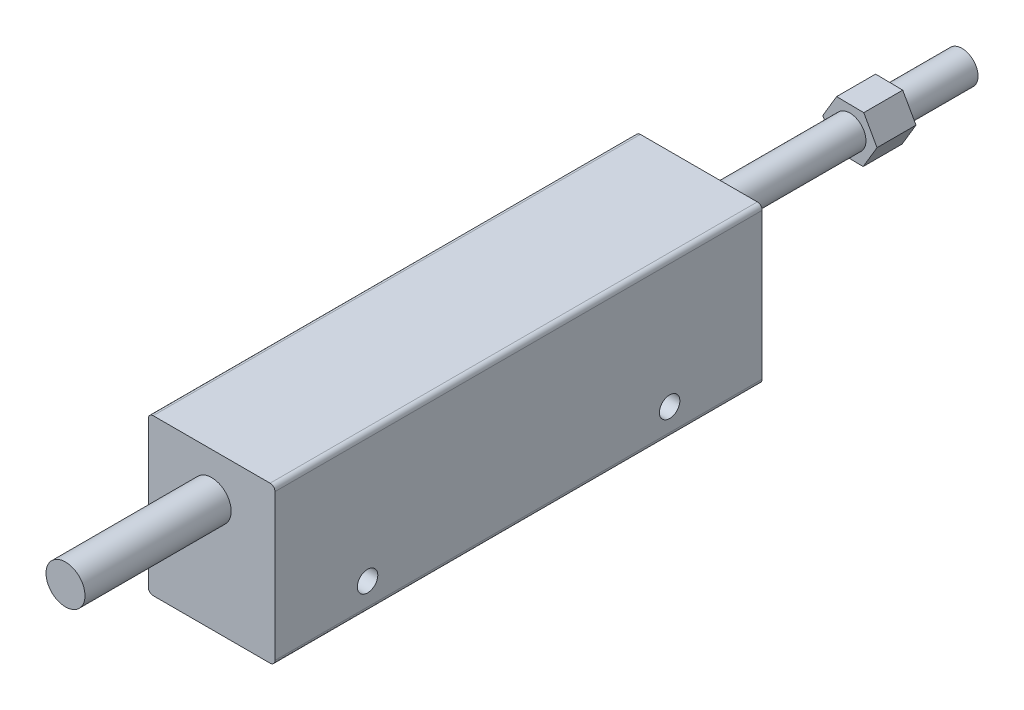
SolidWorks part; units mm, degrees
ref_plane "Front Plane" through (0, 0, 0) normal (0, 0, 1) x (1, 0, 0)
ref_plane "Top Plane" through (0, 0, 0) normal (0, 1, 0) x (1, 0, 0)
ref_plane "Right Plane" through (0, 0, 0) normal (1, 0, 0) x (0, 0, -1)
sketch "Sketch1" plane through (0, 0, 0) normal (0, 0, 1) x (1, 0, 0)
  line L1 (0, 0) -> (13, 0)
  line L2 (0, 0) -> (0, 16)
  line L3 (0, 16) -> (13, 16)
  line L4 (13, 0) -> (13, 16)
  dimension "D1" = 16
  dimension "D2" = 13
extrude "Boss-Extrude1" add sketch "Sketch1" along normal blind 50
sketch "Sketch2" plane through (13, 0, 0) normal (1, 0, 0) x (0, 0, -1)
  line L0 (-50, 0) -> (-50, 16) construction
  line L1 (-50, 0) -> (0, 0) construction
  circle A0 centre (-40.5, 2.8) radius 1.05
  circle A1 centre (-9.5, 2.8) radius 1.05
  point P8 (0, 0)
  dimension "D1" = 2.1
  dimension "D2" = 2.1
  dimension "D3" = 9.5
  dimension "D4" = 31
  dimension "D5" = 2.8
extrude "Cut-Extrude1" cut sketch "Sketch2" against normal through all
sketch "Sketch3" plane through (0, 0, 50) normal (0, 0, 1) x (1, 0, 0)
  line L0 (0, 0) -> (13, 0) construction
  line L1 (13, 16) -> (0, 16) construction
  circle A0 centre (6.5, 11.5) radius 2
  point P4 (0, 0)
  point P7 (6.5, 16)
  dimension "D1" = 4
  dimension "D2" = 11.5
extrude "Boss-Extrude2" add sketch "Sketch3" along normal blind 15
sketch "Sketch4" plane through (0, 0, 0) normal (0, 0, -1) x (-1, 0, 0)
  line L0 (0, 0) -> (-13, 0) construction
  line L1 (-13, 16) -> (0, 16) construction
  circle A0 centre (-6.5, 11.5) radius 1.65
  point P6 (-6.5, 16)
  dimension "D1" = 3.3
  dimension "D2" = 11.5
extrude "Boss-Extrude3" add sketch "Sketch4" along normal blind 27
fillet "Fillet1" radius 0.5 4 edges at (13, 0, 25) (0, 0, 25) (13, 16, 25) (0, 16, 25)
sketch "Sketch6" plane through (0, 0, -27) normal (0, 0, -1) x (-1, 0, 0)
  line L1 (-7.8622, 9.0703) -> (-5.0769, 9.1054)
  line L2 (-5.0769, 9.1054) -> (-3.7147, 11.5351)
  line L3 (-3.7147, 11.5351) -> (-5.1378, 13.9297)
  line L4 (-5.1378, 13.9297) -> (-7.9231, 13.8946)
  line L5 (-7.9231, 13.8946) -> (-9.2853, 11.4649)
  line L6 (-9.2853, 11.4649) -> (-7.8622, 9.0703)
  circle A0 centre (-6.5, 11.5) radius 2.4123 construction
extrude "Boss-Extrude4" add sketch "Sketch6" against normal blind 4 from offset 7.5 offset against normal yes
equation "\"D1@Boss-Extrude2\"=15mm"
equation "\"D1@Boss-Extrude3\"=27.00mm"
